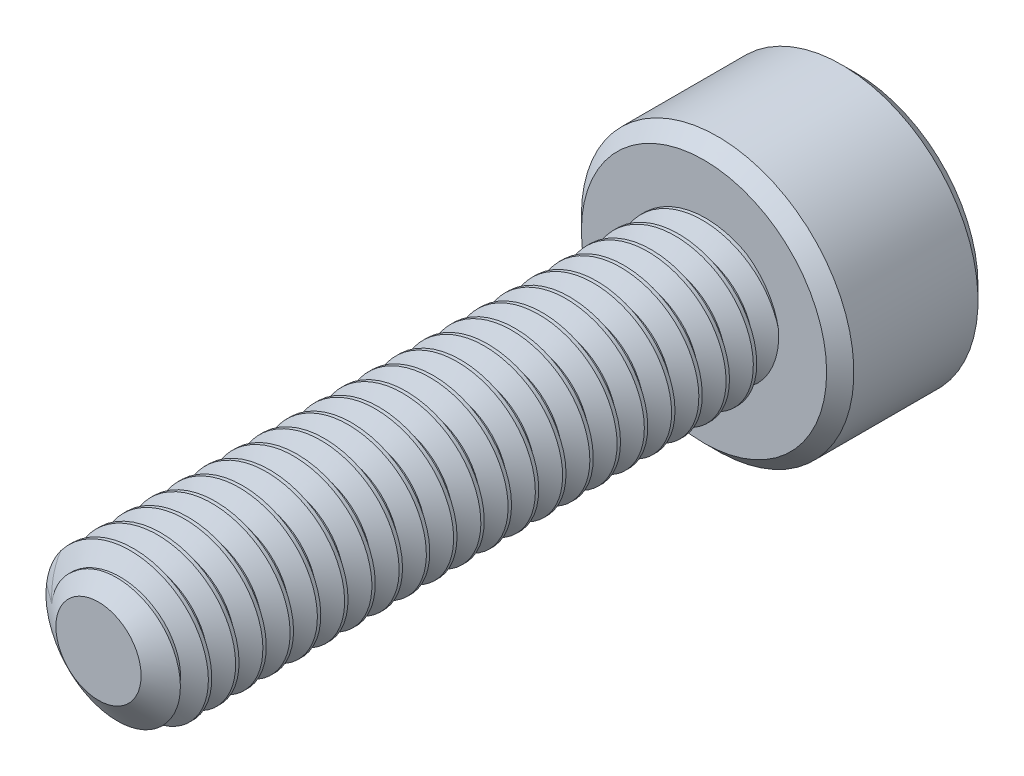
SolidWorks part; units mm, degrees
other "DetailItem1"
material "AISI 304"
ref_plane "Front Plane" through (0, 0, 0) normal (0, 0, 1) x (1, 0, 0)
ref_plane "Top Plane" through (0, 0, 0) normal (0, 1, 0) x (1, 0, 0)
ref_plane "Right Plane" through (0, 0, 0) normal (1, 0, 0) x (0, 0, -1)
sketch "Sketch1" plane through (0, 0, 0) normal (0, 0, 1) x (1, 0, 0)
  circle A0 centre (0, 0) radius 1.25
  dimension "OD" = 2.5
extrude "Extrude1" add sketch "Sketch1" against normal blind 10
sketch "Sketch2" plane through (0, 0, 0) normal (0, 0, 1) x (1, 0, 0)
  circle A0 centre (0, 0) radius 1.25 construction
  circle A1 centre (0, 0) radius 1.25
curve "Helix/Spiral1" pitch 0.45 height 10.45 radius 1.25 centre (0, 0, 0) axis (0, 0, -1) start towards (0, 1, 0) parameters "pitch"=0.45
sketch "Sketch3" plane through (0, 0, 0) normal (1, 0, 0) x (0, 0, -1)
  line L0 (-0.3937, 1.25) -> (-0.225, 0.9577)
  line L1 (-0.225, 0.9577) -> (-0.1688, 0.9577)
  line L2 (-0.1688, 0.9577) -> (0, 1.25)
  line L3 (-0.3937, 1.25) -> (0, 1.25)
  line L4 (-0.1969, 1.25) -> (-0.1969, 0.9577) construction
  line L5 (-0.3094, 1.1039) -> (-0.0844, 1.1039) construction
  line L6 (0, 1.25) -> (0, -1.25) construction
  dimension "D1" = 0.0563
  dimension "D2" = 0.225
  dimension "D3" = 60
sweep "Cut-Sweep1" cut profiles "Sketch3" path "Helix/Spiral1" align with end faces yes
sketch "Sketch4" plane through (0, 0, 0) normal (1, 0, 0) x (0, 0, -1)
  line L0 (0.3825, 1.25) -> (0, 0.7037)
  line L1 (0, 0.7037) -> (0, 1.25)
  line L2 (0.3825, 1.25) -> (0, 1.25)
  line L3 (-0.3937, 1.25) -> (0, 1.25) construction
  line L4 (0, 0) -> (7.0209, 0) construction
  dimension "D1" = 55
  dimension "D2" = 0.254
revolve "Cut-Revolve1" cut sketch "Sketch4" angle 360 about L4
sketch "Sketch6" plane through (0, 0, -10) normal (0, 0, -1) x (-1, 0, 0)
  circle A0 centre (0, 0) radius 2.25
  dimension "head dia" = 4.5
extrude "Extrude2" add sketch "Sketch6" along normal blind 2.5
sketch "Sketch7" plane through (0, 0, -12.5) normal (0, 0, -1) x (-1, 0, 0)
  line L1 (0, 1.1547) -> (-1, 0.5774)
  line L2 (-1, 0.5774) -> (-1, -0.5774)
  line L3 (-1, -0.5774) -> (0, -1.1547)
  line L4 (0, -1.1547) -> (1, -0.5774)
  line L5 (1, -0.5774) -> (1, 0.5774)
  line L6 (1, 0.5774) -> (0, 1.1547)
  circle A0 centre (0, 0) radius 1 construction
  dimension "hex dia" = 2
extrude "Cut-Extrude1" cut sketch "Sketch7" against normal blind 1.5
sketch "Sketch8" plane through (0, 0, -12.5) normal (0, 0, -1) x (-1, 0, 0)
  circle A0 centre (0, 0) radius 1.1547
extrude "Cut-Extrude2" cut sketch "Sketch8" against normal through all draft 45
chamfer "Chamfer1" distance 0.225 angle 45 2 edges at (-2.25, 0, -12.5) (-2.25, 0, -10)
sketch "Sketch10" plane through (0, 0, -10) normal (0, 0, 1) x (1, 0, 0)
  circle A1 centre (0, 0) radius 1.25
  circle A2 centre (0, 0) radius 1.25
  dimension "D1" = 0
ref_plane "Plane1" through (0, 0, 0) normal (0, 0, 1) x (1, 0, 0)
extrude "partial thread" [suppressed] add sketch "Sketch10" along normal up to surface (8 mm away) separate body up to plane "Plane1"
chamfer "Chamfer2" [suppressed] distance 0.05 angle 45
combine bodies "Combine1" [suppressed] operation type add bodies to combine 107 108
sketch "Sketch9" plane through (0, 0, 0) normal (1, 0, 0) x (0, 0, -1)
  line L0 (0, 1.25) -> (0, -1.25) construction
  line L1 (1.125, 1.25) -> (1.125, -1.25) construction
  dimension "D1" = 1.125
equation "\"D3@Helix/Spiral1\" = \"screw length@Extrude1\"+\"pitch@Helix/Spiral1\""
equation "\"D1@Sketch3\" = \"pitch@Helix/Spiral1\"*.125"
equation "\"D2@Sketch3\" = \"pitch@Helix/Spiral1\"*.5"
equation "\"D1@Cut-Extrude1\" = \"hex dia@Sketch7\"*.75"
equation "\"D1@Chamfer1\" = \"head dia@Sketch6\"*.05"
equation "\"D1@Sketch9\" = \"pitch@Helix/Spiral1\"*2.5"
equation "\"D1@Chamfer2\"=\"OD@Sketch1\"*.02"
